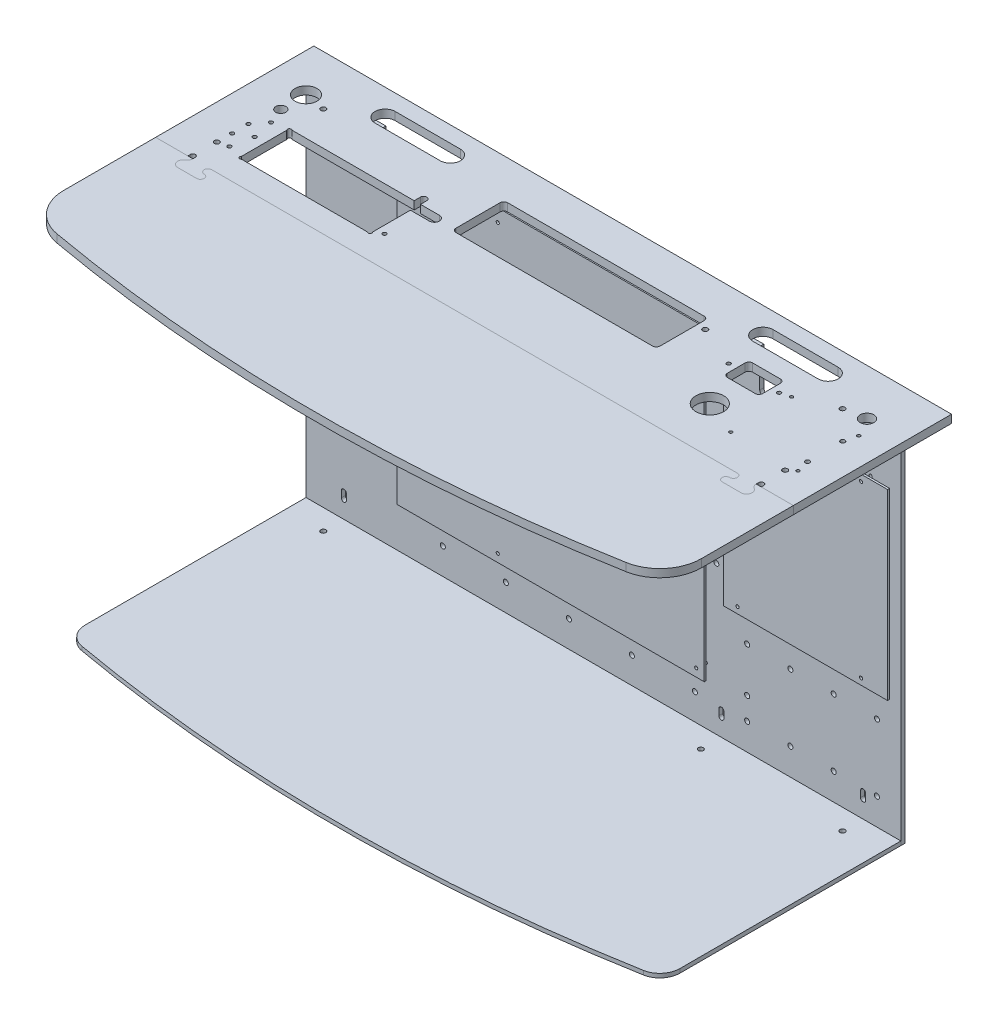
SolidWorks part; units mm, degrees
note: The reader was unsure of these and kept them because the rebuilt part matched: shared geometry of "Sketch19<2>".
other "Backplate"
other "Motherboard"
other "PSU"
other "Top-Front"
other "Top-Rear"
other "Bottom"
ref_plane "Front Plane" through (0, 0, 0) normal (0, 0, 1) x (1, 0, 0)
ref_plane "Top Plane" through (0, 0, 0) normal (0, 1, 0) x (1, 0, 0)
ref_plane "Right Plane" through (0, 0, 0) normal (1, 0, 0) x (0, 0, -1)
sketch "Sketch1" plane through (0, 0, 0) normal (0, 1, 0) x (1, 0, 0)
  line L0 (175.75, 96.8) -> (124, 96.8)
  line L1 (-253, 125.5) -> (253, 125.5)
  line L2 (-253, 125.5) -> (-253, -73.0088)
  line L3 (-253, -73.0088) -> (253, -73.0088) construction
  line L4 (253, 125.5) -> (253, -73.0088)
  line L5 (0, -73.0088) -> (0, 125.5) construction
  line L6 (-253, 26.2456) -> (253, 26.2456) construction
  line L7 (-175.75, 112.8) -> (-124, 112.8)
  line L8 (-175.75, 112.8) -> (-175.75, 96.8) construction
  line L9 (-175.75, 96.8) -> (-124, 96.8)
  line L10 (-124, 112.8) -> (-124, 96.8) construction
  line L11 (-149.875, 96.8) -> (-149.875, 112.8) construction
  line L12 (-175.75, 104.8) -> (-124, 104.8) construction
  line L13 (124, 112.8) -> (124, 96.8) construction
  line L14 (175.75, 112.8) -> (124, 112.8)
  line L15 (175.75, 112.8) -> (175.75, 96.8) construction
  line L16 (0, -125.5) -> (0, 125.5) construction
  line L17 (-1000, 0) -> (49000, 0) construction
  arc A0 (-253, -73.0088) -> (-225.8018, -105.4948) centre (-220, -73.0088) ccw
  arc A1 (253, -73.0088) -> (225.8018, -105.4948) centre (220, -73.0088) cw
  arc A2 (-225.8018, -105.4948) -> (225.8018, -105.4948) centre (0, 1158.8333) ccw
  arc A3 (-175.75, 112.8) -> (-175.75, 96.8) centre (-175.75, 104.8) ccw
  arc A4 (-124, 112.8) -> (-124, 96.8) centre (-124, 104.8) cw
  arc A5 (124, 112.8) -> (124, 96.8) centre (124, 104.8) ccw
  arc A6 (175.75, 112.8) -> (175.75, 96.8) centre (175.75, 104.8) cw
  point P0 (0, 26.2456)
  point P8 (0, -125.5)
  point P9 (-149.875, 104.8)
  point P18 (-124, -119.5)
  dimension "D6" = 33
  dimension "D1" = 506
  dimension "D2" = 251
  dimension "D3" = 351.5
  dimension "D4" = 248
  dimension "D5" = 245
  dimension "D7" = 16
  dimension "D8" = 12.7
extrude "Boss-Extrude1" add sketch "Sketch1" along normal blind 6.35
ref_plane "Plane1" through (0, 0, -105.5) normal (0, 0, -1) x (-1, 0, 0)
sketch "Sketch2" plane through (0, 0, -105.5) normal (0, 0, -1) x (-1, 0, 0)
  line L0 (253, 0) -> (-253, 0) construction
  line L1 (-236, -287) -> (236, -287)
  line L2 (-236, -287) -> (-236, 0)
  line L3 (-236, 0) -> (236, 0)
  line L4 (236, -287) -> (236, 0)
  line L5 (0, 0) -> (0, -287) construction
  line L6 (-236, -143.5) -> (236, -143.5) construction
  point P0 (0, -143.5)
  dimension "D1" = 17
  dimension "D2" = 287
extrude "Boss-Extrude2" add sketch "Sketch2" against normal blind 3.2 separate body
sketch "Sketch3" plane through (0, 0, -102.3) normal (0, 0, 1) x (1, 0, 0)
  line L0 (-172.75, -33) -> (-127, -33)
  line L1 (-175.75, -30) -> (-124, -30) construction
  line L2 (-175.75, -30) -> (-175.75, 0)
  line L3 (-175.75, 0) -> (-124, 0)
  line L4 (-124, -30) -> (-124, 0)
  line L5 (-149.875, 0) -> (-149.875, -30) construction
  line L6 (-175.75, -15) -> (-124, -15) construction
  line L7 (0, 0) -> (0, -287) construction
  line L8 (0, 0) -> (0, -287) construction
  line L9 (124, -30) -> (124, 0)
  line L10 (175.75, 0) -> (124, 0)
  line L11 (175.75, -30) -> (175.75, 0)
  line L12 (172.75, -33) -> (127, -33)
  arc A0 (-175.75, -30) -> (-172.75, -33) centre (-172.75, -30) ccw
  arc A1 (-124, -30) -> (-127, -33) centre (-127, -30) cw
  arc A2 (175.75, -30) -> (172.75, -33) centre (172.75, -30) cw
  arc A3 (124, -30) -> (127, -33) centre (127, -30) ccw
  point P0 (-149.875, -15)
  dimension "D1" = 3
  dimension "D2" = 30
extrude "Cut-Extrude1" cut sketch "Sketch3" against normal through all
ref_plane "Plane2" through (0, 0, -96.3) normal (0, 0, 1) x (1, 0, 0)
sketch "Sketch4" plane through (0, 0, -96.3) normal (0, 0, 1) x (1, 0, 0)
  line L0 (0, 0) -> (0, -287) construction
  line L1 (-156.29, -244.84) -> (87.55, -244.84)
  line L2 (-156.29, -244.84) -> (-156.29, -1)
  line L3 (-156.29, -1) -> (87.55, -1)
  line L4 (87.55, -244.84) -> (87.55, -1)
  line L5 (-34.37, -1) -> (-34.37, -244.84) construction
  line L6 (-156.29, -122.92) -> (87.55, -122.92) construction
  line L8 (-253, 0) -> (253, 0) construction
  circle A0 centre (0, -93.1) radius 30 construction
  circle A1 centre (-122, -11.16) radius 1.25
  circle A2 centre (-76.28, -11.16) radius 1.25
  circle A3 centre (-122, -166.1) radius 1.25
  circle A4 centre (-76.28, -166.1) radius 1.25
  circle A5 centre (-142.32, -166.1) radius 1.25
  circle A6 centre (81.2, -34.02) radius 1.25
  circle A7 centre (-76.28, -238.49) radius 1.25
  circle A8 centre (81.2, -166.1) radius 1.25
  circle A9 centre (81.2, -238.49) radius 1.25
  point P0 (-34.37, -122.92)
  dimension "D1" = 60
  dimension "D3" = 2.5
  dimension "D2" = 243.84
  dimension "D4" = 45.72
  dimension "D5" = 154.94
  dimension "D6" = 203.2
  dimension "D7" = 227.33
  dimension "D8" = 20.32
  dimension "D9" = 10.16
  dimension "D10" = 34.29
  dimension "D11" = 22.86
  dimension "D12" = 122
  dimension "D13" = 73
  dimension "D14" = 1
extrude "Boss-Extrude3" add sketch "Sketch4" along normal blind 1.6 separate body
sketch "Sketch12" plane through (0, 0, -96.3) normal (0, 0, 1) x (1, 0, 0)
  line L0 (236, -287) -> (236, 0) construction
  line L1 (103, -185) -> (233, -185)
  line L2 (103, -185) -> (103, -40)
  line L3 (103, -40) -> (233, -40)
  line L4 (233, -185) -> (233, -40)
  line L5 (168, -40) -> (168, -185) construction
  line L6 (103, -112.5) -> (233, -112.5) construction
  line L7 (-253, 0) -> (253, 0) construction
  line L8 (212, -45) -> (212, -180) construction
  circle A0 centre (212, -45) radius 1.25
  circle A1 centre (212, -180) radius 1.25
  circle A2 centre (114, -180) radius 1.25
  circle A3 centre (114, -45) radius 1.25
  circle A4 centre (81.2, -34.02) radius 1.25 construction
  point P0 (168, -112.5)
  point P18 (212, -112.5)
  dimension "D1" = 130
  dimension "D2" = 3
  dimension "D3" = 40
  dimension "D4" = 135
  dimension "D5" = 98
  dimension "D6" = 11
  dimension "D7" = 145
extrude "Boss-Extrude4" add sketch "Sketch12" along normal blind 1.6 separate body
sketch "Sketch6" plane through (0, 0, -102.3) normal (0, 0, 1) x (1, 0, 0)
  circle A0 centre (-76.28, -238.49) radius 1.25 construction
  circle A1 centre (-76.28, -238.49) radius 1.25
  circle A2 centre (-76.28, -166.1) radius 1.25 construction
  circle A3 centre (-76.28, -166.1) radius 1.25
  circle A4 centre (-122, -166.1) radius 1.25 construction
  circle A5 centre (-122, -166.1) radius 1.25
  circle A6 centre (-142.32, -166.1) radius 1.25 construction
  circle A7 centre (-142.32, -166.1) radius 1.25
  circle A8 centre (81.2, -166.1) radius 1.25 construction
  circle A9 centre (81.2, -166.1) radius 1.25
  circle A10 centre (81.2, -238.49) radius 1.25 construction
  circle A11 centre (81.2, -238.49) radius 1.25
  circle A12 centre (81.2, -34.02) radius 1.25 construction
  circle A13 centre (81.2, -34.02) radius 1.25
  circle A14 centre (-122, -11.16) radius 1.25 construction
  circle A15 centre (-122, -11.16) radius 1.25
  circle A16 centre (-76.28, -11.16) radius 1.25 construction
  circle A17 centre (-76.28, -11.16) radius 1.25
  circle A18 centre (114, -180) radius 1.25 construction
  circle A19 centre (212, -180) radius 1.25 construction
  circle A20 centre (212, -45) radius 1.25 construction
  circle A21 centre (114, -45) radius 1.25 construction
  circle A22 centre (114, -180) radius 1.25
  circle A23 centre (212, -180) radius 1.25
  circle A24 centre (212, -45) radius 1.25
  circle A25 centre (114, -45) radius 1.25
extrude "Cut-Extrude3" cut sketch "Sketch6" against normal through all
sketch "Sketch5" plane through (0, 0, 0) normal (0, -1, 0) x (1, 0, 0)
  line L0 (90.55, -56.7) -> (90.55, -91.7)
  line L1 (-68.45, -94.7) -> (87.55, -94.7)
  line L2 (-68.45, -94.7) -> (-68.45, -53.7) construction
  line L3 (-68.45, -53.7) -> (87.55, -53.7)
  line L4 (87.55, -94.7) -> (87.55, -53.7) construction
  line L5 (9.55, -53.7) -> (9.55, -94.7) construction
  line L6 (-68.45, -74.2) -> (87.55, -74.2) construction
  line L7 (87.55, -94.7) -> (-156.29, -94.7) construction
  line L8 (-71.45, -56.7) -> (-71.45, -91.7)
  arc A0 (-68.45, -53.7) -> (-71.45, -56.7) centre (-68.45, -56.7) ccw
  arc A1 (-68.45, -94.7) -> (-71.45, -91.7) centre (-68.45, -91.7) cw
  arc A2 (87.55, -94.7) -> (90.55, -91.7) centre (87.55, -91.7) ccw
  arc A3 (87.55, -53.7) -> (90.55, -56.7) centre (87.55, -56.7) cw
  point P0 (9.55, -74.2)
  dimension "D1" = 3
  dimension "D2" = 41
  dimension "D3" = 156
extrude "Cut-Extrude2" cut sketch "Sketch5" against normal through all
sketch "Sketch7" plane through (0, 0, 0) normal (0, -1, 0) x (1, 0, 0)
  line L0 (-206, -86) -> (-183.75, -86) construction
  line L1 (97.05, -86) -> (90.55, -86) construction
  line L2 (90.55, -56.7) -> (90.55, -91.7) construction
  line L3 (-124, -102.3) -> (124, -102.3) construction
  line L4 (206, -86) -> (183.75, -86) construction
  circle A0 centre (97.05, -86) radius 2
  circle A1 centre (-206, -86) radius 2
  arc A2 (-175.75, -96.8) -> (-175.75, -112.8) centre (-175.75, -104.8) ccw construction
  circle A3 centre (206, -86) radius 2
  arc A4 (175.75, -112.8) -> (175.75, -96.8) centre (175.75, -104.8) ccw construction
  point P4 (-183.75, -104.8)
  point P17 (183.75, -104.8)
  dimension "D1" = 4
  dimension "D2" = 6.5
  dimension "D3" = 16.3
  dimension "D4" = 30
extrude "Cut-Extrude4" cut sketch "Sketch7" against normal through all
sketch "Sketch8" plane through (0, 0, -102.3) normal (0, 0, 1) x (1, 0, 0)
  line L0 (-236, 0) -> (-175.75, 0) construction
  line L1 (-206, -265) -> (-206, -270) construction
  line L2 (-204, -265) -> (-204, -270)
  line L3 (-208, -265) -> (-208, -270)
  line L4 (93.55, -270) -> (93.55, -265) construction
  line L5 (91.55, -270) -> (91.55, -265)
  line L6 (95.55, -270) -> (95.55, -265)
  line L7 (-236, -287) -> (-236, 0) construction
  line L8 (236, -287) -> (-236, -287) construction
  line L9 (87.55, -244.84) -> (87.55, -1) construction
  line L10 (0, 0) -> (0, -287) construction
  line L11 (0, 0) -> (0, -287) construction
  line L12 (206, -265) -> (206, -270) construction
  line L13 (204, -265) -> (204, -270)
  line L14 (208, -265) -> (208, -270)
  circle A0 centre (-206, -16.3) radius 2
  circle A1 centre (97.05, -16.3) radius 2
  circle A2 centre (206, -16.3) radius 2
  arc A3 (-204, -265) -> (-208, -265) centre (-206, -265) ccw
  arc A4 (-208, -270) -> (-204, -270) centre (-206, -270) ccw
  arc A5 (91.55, -270) -> (95.55, -270) centre (93.55, -270) ccw
  arc A6 (95.55, -265) -> (91.55, -265) centre (93.55, -265) ccw
  arc A7 (204, -265) -> (208, -265) centre (206, -265) cw
  arc A8 (208, -270) -> (204, -270) centre (206, -270) cw
  point P10 (-206, -267.5)
  point P19 (93.55, -267.5)
  point P36 (206, -267.5)
  dimension "D2" = 4
  dimension "D1" = 16.3
  dimension "D3" = 5
  dimension "D4" = 30
  dimension "D5" = 19.5
  dimension "D6" = 6
extrude "Cut-Extrude5" cut sketch "Sketch8" against normal through all
sketch "Sketch9" plane through (0, 0, 0) normal (0, -1, 0) x (1, 0, 0)
  line L0 (175.75, -102.3) -> (236, -102.3) construction
  line L1 (0, 125.5) -> (0, -125.5) construction
  line L2 (0, 125.5) -> (0, -125.5) construction
  circle A0 centre (222.55, -88.85) radius 5.45
  circle A1 centre (-222.55, -88.85) radius 5.45 construction
  circle A2 centre (-222.55, -88.85) radius 8.7313
  circle A3 centre (-222.55, -68.85) radius 4
  point P2 (222.55, -94.3)
  point P3 (228, -88.85)
  dimension "D1" = 10.9
  dimension "D4" = 17.4625
  dimension "D5" = 8
  dimension "D2" = 8
  dimension "D3" = 8
  dimension "D6" = 20
extrude "Cut-Extrude6" cut sketch "Sketch9" against normal through all
sketch "Sketch10" plane through (0, 0, 0) normal (0, -1, 0) x (1, 0, 0)
  line L0 (129.875, -71.8) -> (135.875, -71.8) construction
  line L1 (135.875, -81.8) -> (163.875, -81.8)
  line L2 (135.875, -81.8) -> (135.875, -61.8)
  line L3 (135.875, -61.8) -> (163.875, -61.8)
  line L4 (163.875, -81.8) -> (163.875, -61.8)
  line L5 (149.875, -61.8) -> (149.875, -81.8) construction
  line L6 (135.875, -71.8) -> (163.875, -71.8) construction
  line L7 (169.875, -71.8) -> (163.875, -71.8) construction
  line L8 (175.75, -96.8) -> (124, -96.8) construction
  circle A0 centre (129.875, -71.8) radius 1.5
  circle A1 centre (169.875, -71.8) radius 1.5
  point P0 (149.875, -71.8)
  point P8 (149.875, -96.8)
  dimension "D1" = 3
  dimension "D2" = 40
  dimension "D3" = 20
  dimension "D4" = 28
  dimension "D5" = 15
extrude "Cut-Extrude7" cut sketch "Sketch10" against normal through all
fillet "Fillet1" radius 3 4 edges at (163.875, 3.175, -61.8) (135.875, 3.175, -61.8) (135.875, 3.175, -81.8) (163.875, 3.175, -81.8)
sketch "Sketch11" plane through (0, 0, 0) normal (0, -1, 0) x (1, 0, 0)
  line L0 (149.875, -61.8) -> (149.875, -81.8) construction
  line L1 (135.875, -71.8) -> (163.875, -71.8) construction
  circle A0 centre (149.875, -36.8) radius 11
  dimension "D1" = 22
  dimension "D2" = 35
extrude "Cut-Extrude8" cut sketch "Sketch11" against normal through all
sketch "Sketch13" plane through (0, 0, 0) normal (0, -1, 0) x (1, 0, 0)
  line L0 (-156.29, -96.3) -> (87.55, -96.3) construction
  line L1 (-205.87, -59) -> (-102.87, -59)
  line L2 (-205.87, -59) -> (-205.87, -20)
  line L3 (-205.87, -20) -> (-102.87, -20) construction
  line L4 (-102.87, -59) -> (-102.87, -20) construction
  line L5 (-154.37, -20) -> (-154.37, -59) construction
  line L6 (-205.87, -39.5) -> (-102.87, -39.5) construction
  line L7 (-205.87, -20) -> (-205.87, -19)
  line L8 (-205.87, -19) -> (-101.87, -19)
  line L9 (-101.87, -19) -> (-101.87, -59)
  line L10 (-101.87, -59) -> (-102.87, -59)
  line L11 (-205.87, -57.5) -> (-213.8658, -57.5) construction
  line L12 (-213.8658, -57.5) -> (-216.8658, -54.5) construction
  line L13 (-216.8658, -54.5) -> (-223.87, -54.5) construction
  line L14 (-223.87, -54.5) -> (-223.87, -44.5) construction
  line L15 (-223.87, -44.5) -> (-216.8658, -44.5) construction
  line L16 (-216.8658, -44.5) -> (-211.8658, -39.5) construction
  line L17 (-216.8658, -34.5) -> (-211.8658, -39.5) construction
  line L18 (-223.87, -34.5) -> (-216.8658, -34.5) construction
  line L19 (-223.87, -24.5) -> (-223.87, -34.5) construction
  line L20 (-216.8658, -24.5) -> (-223.87, -24.5) construction
  line L21 (-213.8658, -21.5) -> (-216.8658, -24.5) construction
  line L22 (-205.87, -21.5) -> (-213.8658, -21.5) construction
  line L23 (-201000, 0) -> (249000, 0) construction
  line L24 (-95.87, -54.5) -> (-95.87, -24.5) construction
  circle A0 centre (-213.28, -39.5) radius 1 construction
  circle A1 centre (-213.9871, -39.5) radius 1.5
  circle A3 centre (-217.4871, -56) radius 1.5
  circle A4 centre (-225.37, -46) radius 1.5
  circle A5 centre (-225.37, -33) radius 1.5
  circle A6 centre (-217.4871, -23) radius 1.5
  circle A7 centre (-95.87, -54.5) radius 1.5 construction
  circle A8 centre (-95.87, -24.5) radius 1.5
  point P0 (-154.37, -39.5)
  point P6 (-34.37, -96.3)
  point P41 (-95.87, -39.5)
  dimension "D11" = 2
  dimension "D13" = 3
  dimension "D14" = 3
  dimension "D1" = 103
  dimension "D2" = 120
  dimension "D3" = 19
  dimension "D4" = 39
  dimension "D5" = 1
  dimension "D6" = 1
  dimension "D7" = 36
  dimension "D8" = 121
  dimension "D9" = 10
  dimension "D10" = 3
  dimension "D12" = 10.59
  dimension "D15" = 6
extrude "Cut-Extrude9" cut sketch "Sketch13" against normal through all
sketch "Sketch14" plane through (0, 0, 0) normal (0, -1, 0) x (1, 0, 0)
  line L0 (-204.8093, -20.0607) -> (-205.87, -19) construction
  line L1 (-253, -26.2456) -> (253, -26.2456) construction
  line L2 (-204.8093, -57.9393) -> (-205.87, -59) construction
  line L3 (-102.9307, -20.0607) -> (-101.87, -19) construction
  line L4 (-101.87, -59) -> (-102.9307, -57.9393) construction
  line L5 (-101.87, -59) -> (-101.87, -64)
  line L6 (-106.87, -64) -> (-106.87, -59)
  line L7 (-106.87, -59) -> (-101.87, -59)
  line L8 (-205.87, -59) -> (-102.87, -59) construction
  line L9 (-104.37, -64) -> (-104.37, -66.5) construction
  line L10 (-86.87, -59) -> (-101.87, -59) construction
  line L11 (-101.87, -59) -> (-101.87, -51) construction
  line L12 (-101.87, -51) -> (-86.87, -51) construction
  line L13 (-101.87, -19) -> (-101.87, -59) construction
  line L14 (-223.87, -24.5) -> (-223.87, -34.5) construction
  circle A0 centre (-204.8093, -20.0607) radius 1.5
  circle A1 centre (-204.8093, -57.9393) radius 1.5
  circle A2 centre (-102.9307, -57.9393) radius 1.5 construction
  circle A3 centre (-102.9307, -20.0607) radius 1.5
  arc A4 (-101.87, -64) -> (-106.87, -64) centre (-104.37, -64) cw
  arc A5 (-86.87, -59) -> (-86.87, -51) centre (-86.87, -55) ccw construction
  dimension "D1" = 3
  dimension "D2" = 45
  dimension "D3" = 5
  dimension "D4" = 5
  dimension "D5" = 8
  dimension "D6" = 137
extrude "Cut-Extrude10" cut sketch "Sketch14" against normal through all
sketch "Sketch20" plane through (0, 0, 0) normal (0, -1, 0) x (1, 0, 0)
  line L0 (-101.87, -51) -> (-86.87, -51) construction
  line L1 (-86.87, -59) -> (-101.87, -59) construction
  line L2 (-101.87, -51) -> (-86.87, -51)
  line L3 (-86.87, -59) -> (-101.87, -59)
  line L4 (-101.87, -59) -> (-101.87, -51) construction
  line L5 (-101.87, -59) -> (-101.87, -51)
  arc A0 (-86.87, -59) -> (-86.87, -51) centre (-86.87, -55) ccw construction
  arc A1 (-86.87, -59) -> (-86.87, -51) centre (-86.87, -55) ccw
extrude "Cut-Extrude15" cut sketch "Sketch20" against normal through all
sketch "Sketch15" plane through (0, 0, -102.3) normal (0, 0, 1) x (1, 0, 0)
  line L0 (114, -204) -> (114, -209.5) construction
  line L1 (103, -268) -> (125, -268) construction
  line L2 (103, -268) -> (103, -204) construction
  line L3 (103, -204) -> (125, -204) construction
  line L4 (125, -268) -> (125, -204) construction
  line L5 (114, -209.5) -> (114, -262.5) construction
  line L6 (103, -236) -> (125, -236) construction
  line L7 (114, -262.5) -> (114, -268) construction
  line L8 (103.0597, -185) -> (103.0597, -287) construction
  line L9 (236, -287) -> (-236, -287) construction
  line L10 (103, -185) -> (233, -185) construction
  line L11 (137.3333, -204) -> (159.3333, -204) construction
  line L12 (137.3333, -268) -> (137.3333, -204) construction
  line L13 (137.3333, -268) -> (159.3333, -268) construction
  line L14 (159.3333, -268) -> (159.3333, -204) construction
  line L15 (171.6667, -204) -> (193.6667, -204) construction
  line L16 (171.6667, -268) -> (171.6667, -204) construction
  line L17 (171.6667, -268) -> (193.6667, -268) construction
  line L18 (193.6667, -268) -> (193.6667, -204) construction
  line L19 (206, -204) -> (228, -204) construction
  line L20 (206, -268) -> (206, -204) construction
  line L21 (206, -268) -> (228, -268) construction
  line L22 (228, -268) -> (228, -204) construction
  line L23 (103, -204) -> (137.3333, -204) construction
  line L24 (103, -185) -> (103, -40) construction
  line L25 (233, -185) -> (233, -40) construction
  line L26 (-156.29, -244.84) -> (87.55, -244.84) construction
  line L27 (87.55, -244.84) -> (87.55, -1) construction
  line L28 (72.55, -247.84) -> (72.55, -262.84) construction
  line L29 (72.55, -247.84) -> (22.55, -247.84) construction
  circle A0 centre (114, -209.5) radius 2
  circle A1 centre (114, -262.5) radius 2
  circle A2 centre (148.3333, -262.5) radius 2
  circle A3 centre (148.3333, -209.5) radius 2
  circle A4 centre (182.6667, -262.5) radius 2
  circle A5 centre (182.6667, -209.5) radius 2
  circle A6 centre (217, -262.5) radius 2
  circle A7 centre (217, -209.5) radius 2
  circle A8 centre (114, -189) radius 2
  circle A9 centre (148.3333, -189) radius 2
  circle A10 centre (182.6667, -189) radius 2
  circle A11 centre (217, -189) radius 2
  circle A12 centre (114, -244.84) radius 2
  circle A13 centre (89.55, -84.02) radius 2
  circle A14 centre (101, -84.02) radius 2
  circle A15 centre (89.55, -166.1) radius 2
  circle A16 centre (101, -166.1) radius 2
  circle A17 centre (72.55, -247.84) radius 2
  circle A18 centre (72.55, -262.84) radius 2
  circle A19 centre (22.55, -247.84) radius 2
  circle A20 centre (22.55, -262.84) radius 2
  circle A21 centre (-27.45, -247.84) radius 2
  circle A22 centre (-27.45, -262.84) radius 2
  circle A23 centre (-77.45, -247.84) radius 2
  circle A24 centre (-77.45, -262.84) radius 2
  circle A25 centre (-127.45, -247.84) radius 2
  circle A26 centre (-127.45, -262.84) radius 2
  point P0 (123.3826, -236)
  point P18 (103.0597, -236)
  dimension "D1" = 4
  dimension "D7" = 4
  dimension "D13" = 5
  dimension "D2" = 64
  dimension "D3" = 22
  dimension "D4" = 53
  dimension "D6" = 5
  dimension "D8" = 4
  dimension "D9" = 50
  dimension "D10" = 15
  dimension "D11" = 3
  dimension "D12" = 15
  dimension "D14" = 50
  dimension "D5" = 4
extrude "Cut-Extrude11" cut sketch "Sketch15" against normal through all
sketch "Sketch16" plane through (0, 0, 0) normal (0, -1, 0) x (1, 0, 0)
  line L0 (-253, -125.5) -> (-253, 73.0088) construction
  line L3 (-225.4871, -2) -> (-225.4871, -4) construction
  line L4 (-227.4871, -2) -> (-223.4871, -2) construction
  line L5 (-227.4871, -2) -> (-227.4871, 0)
  line L6 (-227.4871, 0) -> (-223.4871, 0)
  line L7 (-223.4871, -2) -> (-223.4871, 0)
  line L8 (-225.4871, 0) -> (-225.4871, -2) construction
  line L9 (-227.4871, -1) -> (-223.4871, -1) construction
  line L10 (-201000, 0) -> (249000, 0) construction
  line L11 (0, 125.5) -> (0, -125.5) construction
  line L12 (0, 125.5) -> (0, -125.5) construction
  line L13 (223.4871, -2) -> (223.4871, 0)
  line L14 (227.4871, 0) -> (223.4871, 0)
  line L15 (227.4871, -2) -> (227.4871, 0)
  arc A4 (-227.4871, -2) -> (-223.4871, -2) centre (-225.4871, -2) ccw
  circle A5 centre (-225.4871, -21) radius 2
  circle A6 centre (225.4871, -21) radius 2
  arc A7 (227.4871, -2) -> (223.4871, -2) centre (225.4871, -2) cw
  point P0 (-225.4871, -1)
  point P5 (-225.4871, -19)
  dimension "D1" = 4
  dimension "D2" = 15
  dimension "D3" = 8
  dimension "D4" = 27.5129
extrude "Cut-Extrude12" cut sketch "Sketch16" against normal through all
split "Split1" trim tools "Front Plane" bodies to split 116 resulting bodies 117 118
sketch "Sketch17" plane through (0, -287, 0) normal (0, -1, 0) x (1, 0, 0)
  line L1 (236, 73.0088) -> (-236, 73.0088) construction
  line L2 (236, 73.0088) -> (236, -102.3)
  line L3 (236, -102.3) -> (-236, -102.3)
  line L4 (-236, 73.0088) -> (-236, -102.3)
  line L5 (0, -102.3) -> (0, 73.0088) construction
  line L6 (236, -14.6456) -> (-236, -14.6456) construction
  line L7 (236, -102.3) -> (-236, -102.3) construction
  arc A0 (-236, 73.0088) -> (-222.813, 88.7596) centre (-220, 73.0088) cw
  arc A1 (236, 73.0088) -> (222.813, 88.7596) centre (220, 73.0088) ccw
  arc A2 (-222.813, 88.7596) -> (222.813, 88.7596) centre (0, -1158.8333) cw
  arc A3 (-225.8018, 105.4948) -> (-253, 73.0088) centre (-220, 73.0088) ccw construction
  arc A4 (225.8018, 105.4948) -> (-225.8018, 105.4948) centre (0, -1158.8333) ccw construction
  circle A5 centre (-206, -86) radius 2
  circle A6 centre (93.55, -86) radius 2
  circle A7 centre (206, -86) radius 2
  point P0 (0, -14.6456)
  dimension "D1" = 4
  dimension "D2" = 16.3
extrude "Boss-Extrude5" add sketch "Sketch17" against normal blind 3.2 separate body
sketch "Sketch18" plane through (0, 0, 0) normal (0, -1, 0) x (1, 0, 0)
  line L0 (231, -73.85) -> (228.46, -73.85) construction
  line L1 (231, -73.85) -> (231, -71.31) construction
  circle A0 centre (177.66, -25.59) radius 1.25
  circle A1 centre (231, -25.59) radius 1.25
  circle A2 centre (231, -73.85) radius 1.25
  circle A3 centre (177.66, -73.85) radius 1.25
  circle A7 centre (228.46, -35.75) radius 1.75
  circle A8 centre (228.46, -63.69) radius 1.75
  point P0 (231, -73.85)
  point P6 (228.46, -73.85)
  point P7 (225.92, -73.85)
  point P8 (223.38, -73.85)
  point P9 (220.84, -73.85)
  point P10 (218.3, -73.85)
  point P11 (215.76, -73.85)
  point P12 (213.22, -73.85)
  point P13 (210.68, -73.85)
  point P14 (208.14, -73.85)
  point P15 (205.6, -73.85)
  point P16 (203.06, -73.85)
  point P17 (200.52, -73.85)
  point P18 (197.98, -73.85)
  point P19 (195.44, -73.85)
  point P20 (192.9, -73.85)
  point P21 (190.36, -73.85)
  point P22 (187.82, -73.85)
  point P23 (185.28, -73.85)
  point P24 (182.74, -73.85)
  point P25 (180.2, -73.85)
  point P26 (177.66, -73.85)
  point P27 (228.46, -71.31)
  point P28 (225.92, -71.31)
  point P29 (223.38, -71.31)
  point P30 (220.84, -71.31)
  point P31 (218.3, -71.31)
  point P32 (215.76, -71.31)
  point P33 (213.22, -71.31)
  point P34 (210.68, -71.31)
  point P35 (208.14, -71.31)
  point P36 (205.6, -71.31)
  point P37 (203.06, -71.31)
  point P38 (200.52, -71.31)
  point P39 (197.98, -71.31)
  point P40 (195.44, -71.31)
  point P41 (192.9, -71.31)
  point P42 (190.36, -71.31)
  point P43 (187.82, -71.31)
  point P44 (185.28, -71.31)
  point P45 (182.74, -71.31)
  point P46 (180.2, -71.31)
  point P47 (177.66, -71.31)
  point P48 (228.46, -68.77)
  point P49 (225.92, -68.77)
  point P50 (223.38, -68.77)
  point P51 (220.84, -68.77)
  point P52 (218.3, -68.77)
  point P53 (215.76, -68.77)
  point P54 (213.22, -68.77)
  point P55 (210.68, -68.77)
  point P56 (208.14, -68.77)
  point P57 (205.6, -68.77)
  point P58 (203.06, -68.77)
  point P59 (200.52, -68.77)
  point P60 (197.98, -68.77)
  point P61 (195.44, -68.77)
  point P62 (192.9, -68.77)
  point P63 (190.36, -68.77)
  point P64 (187.82, -68.77)
  point P65 (185.28, -68.77)
  point P66 (182.74, -68.77)
  point P67 (180.2, -68.77)
  point P68 (177.66, -68.77)
  point P69 (228.46, -66.23)
  point P70 (225.92, -66.23)
  point P71 (223.38, -66.23)
  point P72 (220.84, -66.23)
  point P73 (218.3, -66.23)
  point P74 (215.76, -66.23)
  point P75 (213.22, -66.23)
  point P76 (210.68, -66.23)
  point P77 (208.14, -66.23)
  point P78 (205.6, -66.23)
  point P79 (203.06, -66.23)
  point P80 (200.52, -66.23)
  point P81 (197.98, -66.23)
  point P82 (195.44, -66.23)
  point P83 (192.9, -66.23)
  point P84 (190.36, -66.23)
  point P85 (187.82, -66.23)
  point P86 (185.28, -66.23)
  point P87 (182.74, -66.23)
  point P88 (180.2, -66.23)
  point P89 (177.66, -66.23)
  point P90 (228.46, -63.69)
  point P91 (225.92, -63.69)
  point P92 (223.38, -63.69)
  point P93 (220.84, -63.69)
  point P94 (218.3, -63.69)
  point P95 (215.76, -63.69)
  point P96 (213.22, -63.69)
  point P97 (210.68, -63.69)
  point P98 (208.14, -63.69)
  point P99 (205.6, -63.69)
  point P100 (203.06, -63.69)
  point P101 (200.52, -63.69)
  point P102 (197.98, -63.69)
  point P103 (195.44, -63.69)
  point P104 (192.9, -63.69)
  point P105 (190.36, -63.69)
  point P106 (187.82, -63.69)
  point P107 (185.28, -63.69)
  point P108 (182.74, -63.69)
  point P109 (180.2, -63.69)
  point P110 (177.66, -63.69)
  point P111 (228.46, -61.15)
  point P112 (225.92, -61.15)
  point P113 (223.38, -61.15)
  point P114 (220.84, -61.15)
  point P115 (218.3, -61.15)
  point P116 (215.76, -61.15)
  point P117 (213.22, -61.15)
  point P118 (210.68, -61.15)
  point P119 (208.14, -61.15)
  point P120 (205.6, -61.15)
  point P121 (203.06, -61.15)
  point P122 (200.52, -61.15)
  point P123 (197.98, -61.15)
  point P124 (195.44, -61.15)
  point P125 (192.9, -61.15)
  point P126 (190.36, -61.15)
  point P127 (187.82, -61.15)
  point P128 (185.28, -61.15)
  point P129 (182.74, -61.15)
  point P130 (180.2, -61.15)
  point P131 (177.66, -61.15)
  point P132 (228.46, -58.61)
  point P133 (225.92, -58.61)
  point P134 (223.38, -58.61)
  point P135 (220.84, -58.61)
  point P136 (218.3, -58.61)
  point P137 (215.76, -58.61)
  point P138 (213.22, -58.61)
  point P139 (210.68, -58.61)
  point P140 (208.14, -58.61)
  point P141 (205.6, -58.61)
  point P142 (203.06, -58.61)
  point P143 (200.52, -58.61)
  point P144 (197.98, -58.61)
  point P145 (195.44, -58.61)
  point P146 (192.9, -58.61)
  point P147 (190.36, -58.61)
  point P148 (187.82, -58.61)
  point P149 (185.28, -58.61)
  point P150 (182.74, -58.61)
  point P151 (180.2, -58.61)
  point P152 (177.66, -58.61)
  point P153 (228.46, -56.07)
  point P154 (225.92, -56.07)
  point P155 (223.38, -56.07)
  point P156 (220.84, -56.07)
  point P157 (218.3, -56.07)
  point P158 (215.76, -56.07)
  point P159 (213.22, -56.07)
  point P160 (210.68, -56.07)
  point P161 (208.14, -56.07)
  point P162 (205.6, -56.07)
  point P163 (203.06, -56.07)
  point P164 (200.52, -56.07)
  point P165 (197.98, -56.07)
  point P166 (195.44, -56.07)
  point P167 (192.9, -56.07)
  point P168 (190.36, -56.07)
  point P169 (187.82, -56.07)
  point P170 (185.28, -56.07)
  point P171 (182.74, -56.07)
  point P172 (180.2, -56.07)
  point P173 (177.66, -56.07)
  point P174 (228.46, -53.53)
  point P175 (225.92, -53.53)
  point P176 (223.38, -53.53)
  point P177 (220.84, -53.53)
  point P178 (218.3, -53.53)
  point P179 (215.76, -53.53)
  point P180 (213.22, -53.53)
  point P181 (210.68, -53.53)
  point P182 (208.14, -53.53)
  point P183 (205.6, -53.53)
  point P184 (203.06, -53.53)
  point P185 (200.52, -53.53)
  point P186 (197.98, -53.53)
  point P187 (195.44, -53.53)
  point P188 (192.9, -53.53)
  point P189 (190.36, -53.53)
  point P190 (187.82, -53.53)
  point P191 (185.28, -53.53)
  point P192 (182.74, -53.53)
  point P193 (180.2, -53.53)
  point P194 (177.66, -53.53)
  point P195 (228.46, -50.99)
  point P196 (225.92, -50.99)
  point P197 (223.38, -50.99)
  point P198 (220.84, -50.99)
  point P199 (218.3, -50.99)
  point P200 (215.76, -50.99)
  point P201 (213.22, -50.99)
  point P202 (210.68, -50.99)
  point P203 (208.14, -50.99)
  point P204 (205.6, -50.99)
  point P205 (203.06, -50.99)
  point P206 (200.52, -50.99)
  point P207 (197.98, -50.99)
  point P208 (195.44, -50.99)
  point P209 (192.9, -50.99)
  point P210 (190.36, -50.99)
  point P211 (187.82, -50.99)
  point P212 (185.28, -50.99)
  point P213 (182.74, -50.99)
  point P214 (180.2, -50.99)
  point P215 (177.66, -50.99)
  point P216 (228.46, -48.45)
  point P217 (225.92, -48.45)
  point P218 (223.38, -48.45)
  point P219 (220.84, -48.45)
  point P220 (218.3, -48.45)
  point P221 (215.76, -48.45)
  point P222 (213.22, -48.45)
  point P223 (210.68, -48.45)
  point P224 (208.14, -48.45)
  point P225 (205.6, -48.45)
  point P226 (203.06, -48.45)
  point P227 (200.52, -48.45)
  point P228 (197.98, -48.45)
  point P229 (195.44, -48.45)
  point P230 (192.9, -48.45)
  point P231 (190.36, -48.45)
  point P232 (187.82, -48.45)
  point P233 (185.28, -48.45)
  point P234 (182.74, -48.45)
  point P235 (180.2, -48.45)
  point P236 (177.66, -48.45)
  point P237 (228.46, -45.91)
  point P238 (225.92, -45.91)
  point P239 (223.38, -45.91)
  point P240 (220.84, -45.91)
  point P241 (218.3, -45.91)
  point P242 (215.76, -45.91)
  point P243 (213.22, -45.91)
  point P244 (210.68, -45.91)
  point P245 (208.14, -45.91)
  point P246 (205.6, -45.91)
  point P247 (203.06, -45.91)
  point P248 (200.52, -45.91)
  point P249 (197.98, -45.91)
  point P250 (195.44, -45.91)
  point P251 (192.9, -45.91)
  point P252 (190.36, -45.91)
  point P253 (187.82, -45.91)
  point P254 (185.28, -45.91)
  point P255 (182.74, -45.91)
  point P256 (180.2, -45.91)
  point P257 (177.66, -45.91)
  point P258 (228.46, -43.37)
  point P259 (225.92, -43.37)
  point P260 (223.38, -43.37)
  point P261 (220.84, -43.37)
  point P262 (218.3, -43.37)
  point P263 (215.76, -43.37)
  point P264 (213.22, -43.37)
  point P265 (210.68, -43.37)
  point P266 (208.14, -43.37)
  point P267 (205.6, -43.37)
  point P268 (203.06, -43.37)
  point P269 (200.52, -43.37)
  point P270 (197.98, -43.37)
  point P271 (195.44, -43.37)
  point P272 (192.9, -43.37)
  point P273 (190.36, -43.37)
  point P274 (187.82, -43.37)
  point P275 (185.28, -43.37)
  point P276 (182.74, -43.37)
  point P277 (180.2, -43.37)
  point P278 (177.66, -43.37)
  point P279 (228.46, -40.83)
  point P280 (225.92, -40.83)
  point P281 (223.38, -40.83)
  point P282 (220.84, -40.83)
  point P283 (218.3, -40.83)
  point P284 (215.76, -40.83)
  point P285 (213.22, -40.83)
  point P286 (210.68, -40.83)
  point P287 (208.14, -40.83)
  point P288 (205.6, -40.83)
  point P289 (203.06, -40.83)
  point P290 (200.52, -40.83)
  point P291 (197.98, -40.83)
  point P292 (195.44, -40.83)
  point P293 (192.9, -40.83)
  point P294 (190.36, -40.83)
  point P295 (187.82, -40.83)
  point P296 (185.28, -40.83)
  point P297 (182.74, -40.83)
  point P298 (180.2, -40.83)
  point P299 (177.66, -40.83)
  point P300 (228.46, -38.29)
  point P301 (225.92, -38.29)
  point P302 (223.38, -38.29)
  point P303 (220.84, -38.29)
  point P304 (218.3, -38.29)
  point P305 (215.76, -38.29)
  point P306 (213.22, -38.29)
  point P307 (210.68, -38.29)
  point P308 (208.14, -38.29)
  point P309 (205.6, -38.29)
  point P310 (203.06, -38.29)
  point P311 (200.52, -38.29)
  point P312 (197.98, -38.29)
  point P313 (195.44, -38.29)
  point P314 (192.9, -38.29)
  point P315 (190.36, -38.29)
  point P316 (187.82, -38.29)
  point P317 (185.28, -38.29)
  point P318 (182.74, -38.29)
  point P319 (180.2, -38.29)
  point P320 (177.66, -38.29)
  point P321 (228.46, -35.75)
  point P322 (225.92, -35.75)
  point P323 (223.38, -35.75)
  point P324 (220.84, -35.75)
  point P325 (218.3, -35.75)
  point P326 (215.76, -35.75)
  point P327 (213.22, -35.75)
  point P328 (210.68, -35.75)
  point P329 (208.14, -35.75)
  point P330 (205.6, -35.75)
  point P331 (203.06, -35.75)
  point P332 (200.52, -35.75)
  point P333 (197.98, -35.75)
  point P334 (195.44, -35.75)
  point P335 (192.9, -35.75)
  point P336 (190.36, -35.75)
  point P337 (187.82, -35.75)
  point P338 (185.28, -35.75)
  point P339 (182.74, -35.75)
  point P340 (180.2, -35.75)
  point P341 (177.66, -35.75)
  point P342 (228.46, -33.21)
  point P343 (225.92, -33.21)
  point P344 (223.38, -33.21)
  point P345 (220.84, -33.21)
  point P346 (218.3, -33.21)
  point P347 (215.76, -33.21)
  point P348 (213.22, -33.21)
  point P349 (210.68, -33.21)
  point P350 (208.14, -33.21)
  point P351 (205.6, -33.21)
  point P352 (203.06, -33.21)
  point P353 (200.52, -33.21)
  point P354 (197.98, -33.21)
  point P355 (195.44, -33.21)
  point P356 (192.9, -33.21)
  point P357 (190.36, -33.21)
  point P358 (187.82, -33.21)
  point P359 (185.28, -33.21)
  point P360 (182.74, -33.21)
  point P361 (180.2, -33.21)
  point P362 (177.66, -33.21)
  point P363 (228.46, -30.67)
  point P364 (225.92, -30.67)
  point P365 (223.38, -30.67)
  point P366 (220.84, -30.67)
  point P367 (218.3, -30.67)
  point P368 (215.76, -30.67)
  point P369 (213.22, -30.67)
  point P370 (210.68, -30.67)
  point P371 (208.14, -30.67)
  point P372 (205.6, -30.67)
  point P373 (203.06, -30.67)
  point P374 (200.52, -30.67)
  point P375 (197.98, -30.67)
  point P376 (195.44, -30.67)
  point P377 (192.9, -30.67)
  point P378 (190.36, -30.67)
  point P379 (187.82, -30.67)
  point P380 (185.28, -30.67)
  point P381 (182.74, -30.67)
  point P382 (180.2, -30.67)
  point P383 (177.66, -30.67)
  point P384 (228.46, -28.13)
  point P385 (225.92, -28.13)
  point P386 (223.38, -28.13)
  point P387 (220.84, -28.13)
  point P388 (218.3, -28.13)
  point P389 (215.76, -28.13)
  point P390 (213.22, -28.13)
  point P391 (210.68, -28.13)
  point P392 (208.14, -28.13)
  point P393 (205.6, -28.13)
  point P394 (203.06, -28.13)
  point P395 (200.52, -28.13)
  point P396 (197.98, -28.13)
  point P397 (195.44, -28.13)
  point P398 (192.9, -28.13)
  point P399 (190.36, -28.13)
  point P400 (187.82, -28.13)
  point P401 (185.28, -28.13)
  point P402 (182.74, -28.13)
  point P403 (180.2, -28.13)
  point P404 (177.66, -28.13)
  point P405 (228.46, -25.59)
  point P406 (225.92, -25.59)
  point P407 (223.38, -25.59)
  point P408 (220.84, -25.59)
  point P409 (218.3, -25.59)
  point P410 (215.76, -25.59)
  point P411 (213.22, -25.59)
  point P412 (210.68, -25.59)
  point P413 (208.14, -25.59)
  point P414 (205.6, -25.59)
  point P415 (203.06, -25.59)
  point P416 (200.52, -25.59)
  point P417 (197.98, -25.59)
  point P418 (195.44, -25.59)
  point P419 (192.9, -25.59)
  point P420 (190.36, -25.59)
  point P421 (187.82, -25.59)
  point P422 (185.28, -25.59)
  point P423 (182.74, -25.59)
  point P424 (180.2, -25.59)
  point P425 (177.66, -25.59)
  point P426 (231, -71.31)
  point P427 (231, -68.77)
  point P428 (231, -66.23)
  point P429 (231, -63.69)
  point P430 (231, -61.15)
  point P431 (231, -58.61)
  point P432 (231, -56.07)
  point P433 (231, -53.53)
  point P434 (231, -50.99)
  point P435 (231, -48.45)
  point P436 (231, -45.91)
  point P437 (231, -43.37)
  point P438 (231, -40.83)
  point P439 (231, -38.29)
  point P440 (231, -35.75)
  point P441 (231, -33.21)
  point P442 (231, -30.67)
  point P443 (231, -28.13)
  point P444 (231, -25.59)
  dimension "D6" = 2.5
  dimension "D7" = 3.5
  dimension "D1" = 5
  dimension "D2" = 15
  dimension "D5" = 2.54
  dimension "D3" = 22
  dimension "D4" = 20
extrude "Cut-Extrude13" cut sketch "Sketch18" against normal through all
sketch "Sketch19" plane through (0, 0, 0) normal (0, -1, 0) x (1, 0, 0)
  line L0 (-223.4871, 12) -> (-208.4871, 12)
  line L1 (-223.4871, -2) -> (-223.4871, 0) construction
  line L2 (-201000, 0) -> (249000, 0) construction
  line L3 (-223.4871, 0) -> (-208.4871, 0)
  line L4 (0, 125.5) -> (0, -125.5) construction
  line L5 (0, 125.5) -> (0, -125.5) construction
  line L6 (223.4871, 12) -> (208.4871, 12)
  line L7 (223.4871, 0) -> (208.4871, 0)
  arc A0 (-223.4871, 0) -> (-225.6833, 3.8038) centre (-227.8794, 0) ccw
  arc A1 (-225.6833, 3.8038) -> (-223.4871, 12) centre (-223.4871, 7.6077) cw
  arc A2 (-208.4871, 12) -> (-208.4871, 6) centre (-208.4871, 9) cw
  arc A3 (-208.4871, 6) -> (-208.4871, 0) centre (-208.4871, 3) ccw
  arc A4 (223.4871, 0) -> (225.6833, 3.8038) centre (227.8794, 0) cw
  arc A5 (225.6833, 3.8038) -> (223.4871, 12) centre (223.4871, 7.6077) ccw
  arc A6 (208.4871, 12) -> (208.4871, 6) centre (208.4871, 9) ccw
  arc A7 (208.4871, 6) -> (208.4871, 0) centre (208.4871, 3) cw
  dimension "D2" = 3
  dimension "D1" = 15
extrude "Boss-Extrude6" add sketch "Sketch19" against normal up to surface (6.35 mm away) up to face at (228.46, 6.35, -37.5)
extrude "Cut-Extrude14" cut sketch "Sketch19<2>" against normal through all
sketch "Sketch19<2>" plane through (0, 0, 0) normal (0, -1, 0) x (1, 0, 0) same geometry as "Sketch19"
